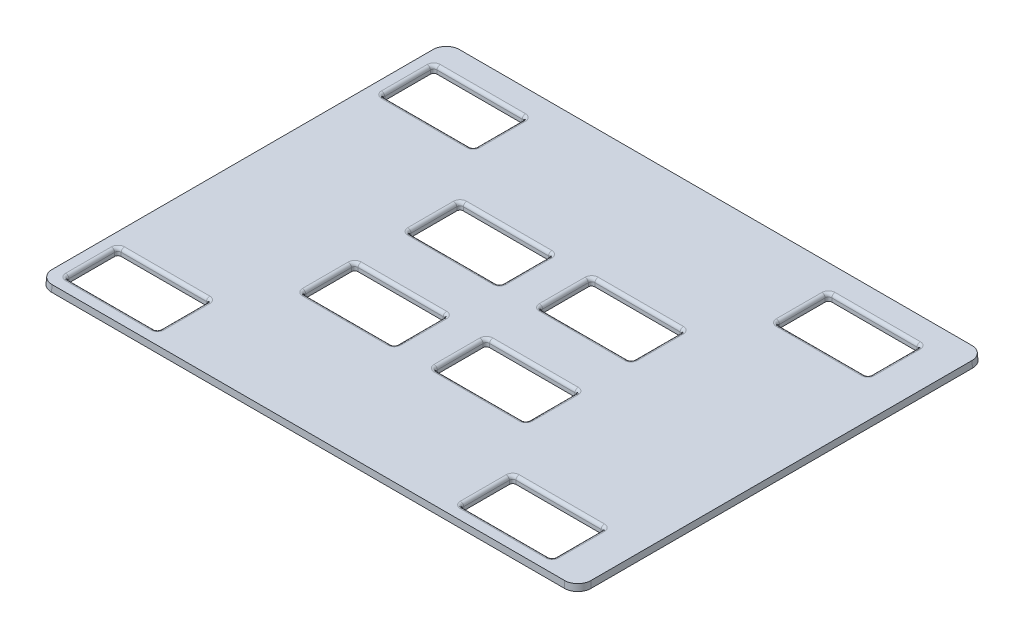
SolidWorks part; units mm, degrees
ref_plane "Front" through (0, 0, 0) normal (0, 0, 1) x (1, 0, 0)
ref_plane "Top" through (0, 0, 0) normal (0, 1, 0) x (1, 0, 0)
ref_plane "Right" through (0, 0, 0) normal (1, 0, 0) x (0, 0, -1)
sketch "Sketch1" plane through (0, 0, 0) normal (0, 1, 0) x (1, 0, 0)
  line L1 (0, 0) -> (260.35, 0)
  line L2 (0, 0) -> (0, 196.85)
  line L3 (0, 196.85) -> (260.35, 196.85)
  line L4 (260.35, 0) -> (260.35, 196.85)
  dimension "D1" = 260.35
  dimension "D2" = 196.85
extrude "Extrude1" add sketch "Sketch1" along normal blind 3.175 draft 3
fillet "Fillet3" radius 6.35 4 edges at (0.0832, 1.5875, -196.7668) (260.2668, 1.5875, -196.7668) (260.2668, 1.5875, -0.0832) (0.0832, 1.5875, -0.0832)
sketch "Sketch2" plane through (0, 3.175, 0) normal (0, 1, 0) x (-1, 0, 0)
  line L0 (-0.1664, -190.3423) -> (-0.1664, -6.5077) construction
  line L1 (-6.5164, -6.5164) -> (-50.9664, -6.5164)
  line L2 (-6.5164, -6.5164) -> (-6.5164, -31.9164)
  line L3 (-6.5164, -31.9164) -> (-50.9664, -31.9164)
  line L4 (-50.9664, -6.5164) -> (-50.9664, -31.9164)
  line L5 (-6.5077, -0.1664) -> (-253.8423, -0.1664) construction
  dimension "D1" = 6.35
  dimension "D2" = 6.35
  dimension "D3" = 44.45
  dimension "D4" = 25.4
extrude "Cut-Extrude1" cut sketch "Sketch2" against normal through all draft 3
fillet "Fillet1" radius 1.5875 4 edges at (50.8832, 1.5875, -31.8332) (50.8832, 1.5875, -6.5996) (6.5996, 1.5875, -6.5996) (6.5996, 1.5875, -31.8332)
fillet "Fillet2" radius 1.5875 8 edges at (6.9805, 3.175, -6.9805) (6.5164, 3.175, -19.2164) (6.9805, 3.175, -31.4523) (28.7414, 3.175, -31.9164) (50.5023, 3.175, -31.4523) (50.9664, 3.175, -19.2164) (50.5023, 3.175, -6.9805) (28.7414, 3.175, -6.5164)
pattern_linear "LPattern1" count 4 spacing 50.8 along (0, 0, -1) count 4 spacing 63.5 along (1, 0, 0) skipping (0, 1), (0, 2), (1, 0), (1, 3), (2, 0), (2, 3), (3, 1), (3, 2) of "Fillet2", "Cut-Extrude1", "Fillet1"
